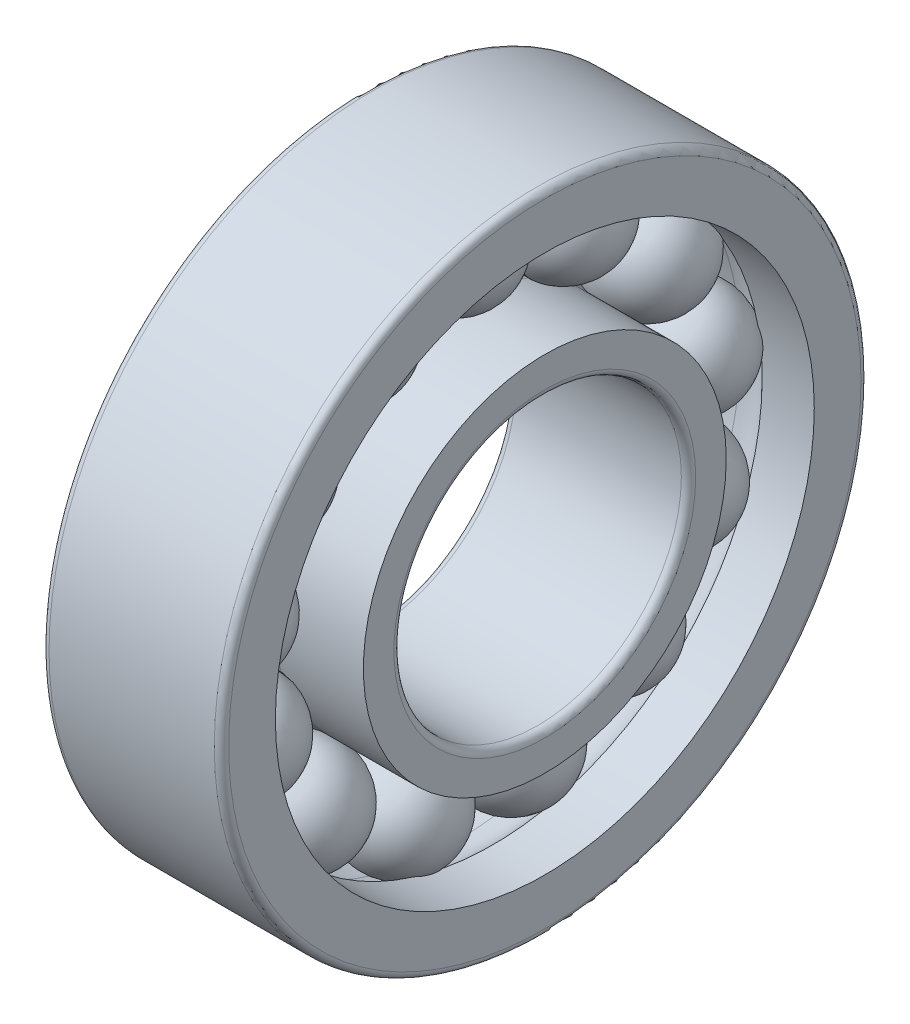
SolidWorks part; units mm, degrees
ref_plane "Plane1" through (0, 0, 0) normal (0, 0, 1) x (1, 0, 0)
ref_plane "Plane2" through (0, 0, 0) normal (0, 1, 0) x (1, 0, 0)
ref_plane "Plane3" through (0, 0, 0) normal (1, 0, 0) x (0, 0, -1)
sketch "Clipboard" plane through (0, 0, 0) normal (0, 0, 1) x (1, 0, 0)
  line L0 (-10, 0) -> (10, 0) construction
  line L1 (0, 0) -> (21.7876, -5.0301)
  line L2 (0, 0) -> (3.2495, -0.0567)
  line L3 (0, 0) -> (22.3573, 0.3902)
  line L4 (0, 0) -> (-22.3573, -0.3902)
  dimension "BallCLRad" = 3.25
sketch "CagSpiSke" plane through (0, 0, 0) normal (0, 0, 1) x (1, 0, 0)
  line L0 (0.1875, 3.125) -> (0.1875, 3.375)
  line L1 (0.1875, 3.375) -> (-0.1875, 3.375)
  line L2 (-0.1875, 3.375) -> (-0.1875, 3.125)
  line L3 (-0.1875, 3.125) -> (0.1875, 3.125)
  line L4 (-20.6375, 0) -> (20.6375, 0) construction
  line L5 (0, 0) -> (0, 23.7692) construction
  dimension "OD" = 6.75
  dimension "ID" = 6.25
revolve "CageSpine" add sketch "CagSpiSke" angle 0.001 about L4
ref_axis "Axis1" through (-50, 0, 0) along (1, 0, 0)
sketch "CagBalSke" plane through (0, 0, 0) normal (0, 0, 1) x (1, 0, 0)
  line L0 (-0.825, 3.25) -> (0.825, 3.25)
  line L1 (-1.905, 3.25) -> (1.905, 3.25) construction
  line L2 (-10, 0) -> (10, 0) construction
  line L3 (0, 0) -> (0, 24) construction
  arc A0 (0.825, 3.25) -> (-0.825, 3.25) centre (0, 3.25) cw
  dimension "BallCLRad" = 3.25
revolve "CageBall" [suppressed] add sketch "CagBalSke" angle 360 about L1 reverse direction yes
pattern_circular "CageBalls" [suppressed] count 13 every 27.692 about axis through (-50, 0, 0) along (1, 0, 0)
sketch "CagTrmODSke" plane through (0, 0, 0) normal (0, 0, 1) x (1, 0, 0)
  line L0 (0.826, 3.375) -> (0.826, 4.076)
  line L1 (0.826, 4.076) -> (-0.826, 4.076)
  line L2 (-0.826, 4.076) -> (-0.826, 3.375)
  line L3 (-0.826, 3.375) -> (0.826, 3.375)
  line L4 (-20.6375, 0) -> (20.6375, 0) construction
  line L5 (0, 0) -> (0, 25) construction
  dimension "Width" = 1.652
  dimension "ID" = 6.75
  dimension "OD" = 8.152
revolve "CageTrimOD" [suppressed] cut sketch "CagTrmODSke" angle 360 about L4 reverse direction yes
sketch "CagTrmIDSke" plane through (0, 0, 0) normal (0, 0, 1) x (1, 0, 0)
  line L0 (0.826, 2.426) -> (0.826, 3.125)
  line L1 (0.826, 3.125) -> (-0.826, 3.125)
  line L2 (-0.826, 3.125) -> (-0.826, 2.426)
  line L3 (-0.826, 2.426) -> (0.826, 2.426)
  line L4 (-20.6375, 0) -> (20.6375, 0) construction
  line L5 (0, 0) -> (0, 25) construction
  dimension "Width" = 1.652
  dimension "ID" = 4.852
  dimension "OD" = 6.25
revolve "CageTrimID" [suppressed] cut sketch "CagTrmIDSke" angle 360 about L4 reverse direction yes
sketch "BalSimSke" plane through (0, 0, 0) normal (0, 0, 1) x (1, 0, 0)
  line L0 (-10, 0) -> (10, 0) construction
  line L1 (-10, 3.25) -> (10, 3.25) construction
  line L2 (0, 0) -> (0, 23) construction
  circle A0 centre (0, 3.25) radius 0.75
  dimension "BallCLRad" = 3.25
  dimension "Ball_diameter" = 1.5
revolve "BallsSimplified" [suppressed] add sketch "BalSimSke" angle 360 about L0
sketch "BalDetSke" plane through (0, 0, 0) normal (0, 0, 1) x (1, 0, 0)
  line L0 (-0.75, 3.25) -> (0.75, 3.25)
  line L1 (-1.905, 3.25) -> (1.905, 3.25) construction
  line L2 (0, 0) -> (0, 25) construction
  arc A0 (0.75, 3.25) -> (-0.75, 3.25) centre (0, 3.25) cw
  dimension "BallCLRad" = 3.25
  dimension "Ball_diameter" = 1.5
revolve "BallDetailed" add sketch "BalDetSke" angle 360 about L1 reverse direction yes
sketch "InnRacSke" plane through (0, 0, 0) normal (0, 0, 1) x (1, 0, 0)
  line L0 (-0.525, 2.75) -> (-1.25, 2.75)
  line L1 (-1.25, 2.75) -> (-1.25, 2.1)
  line L2 (-1.15, 2) -> (1.15, 2)
  line L3 (1.25, 2.1) -> (1.25, 2.525)
  line L4 (0, 2.525) -> (1.25, 2.525)
  line L5 (-20.6375, 0) -> (20.6375, 0) construction
  line L6 (0, 0) -> (0, 30) construction
  arc A0 (-1.25, 2.1) -> (-1.15, 2) centre (-1.15, 2.1) ccw
  arc A1 (1.15, 2) -> (1.25, 2.1) centre (1.15, 2.1) ccw
  arc A2 (0, 2.525) -> (-0.525, 2.75) centre (0, 3.25) cw
  dimension "BallCLRad" = 3.25
  dimension "Fillet_radius" = 0.1
  dimension "Ball_diameter" = 1.45
  dimension "ID" = 4
  dimension "OD" = 5.5
  dimension "Width" = 2.5
revolve "InnerRace" add sketch "InnRacSke" angle 360 about L5 reverse direction yes
sketch "OutRacSke" plane through (0, 0, 0) normal (0, 0, 1) x (1, 0, 0)
  line L0 (0, 3.975) -> (-1.25, 3.975)
  line L1 (-1.25, 3.975) -> (-1.25, 4.4)
  line L2 (-1.15, 4.5) -> (1.15, 4.5)
  line L3 (1.25, 4.4) -> (1.25, 3.75)
  line L4 (1.25, 3.75) -> (0.525, 3.75)
  line L5 (-20.6375, 0) -> (20.6375, 0) construction
  line L6 (0, 0) -> (0, 30) construction
  arc A0 (-1.25, 4.4) -> (-1.15, 4.5) centre (-1.15, 4.4) cw
  arc A1 (1.15, 4.5) -> (1.25, 4.4) centre (1.15, 4.4) cw
  arc A2 (0.525, 3.75) -> (0, 3.975) centre (0, 3.25) ccw
  dimension "BallCLRad" = 3.25
  dimension "Fillet_radius" = 0.1
  dimension "Ball_diameter" = 1.45
  dimension "Width" = 2.5
revolve "OuterRace" add sketch "OutRacSke" angle 360 about L5 reverse direction yes
pattern_circular "BallsDetailed" count 13 every 27.692 about axis through (-50, 0, 0) along (1, 0, 0) of "BallDetailed"
equation "\"BallCLRad@Clipboard\" = ( \"OD@OutRacSke\" + \"ID@InnRacSke\" ) / 4"
equation "\"BallCLRad@BalSimSke\" = \"BallCLRad@Clipboard\""
equation "\"BallCLRad@BalDetSke\" = \"BallCLRad@Clipboard\""
equation "\"BallCLRad@InnRacSke\" = \"BallCLRad@Clipboard\""
equation "\"BallCLRad@OutRacSke\" = \"BallCLRad@Clipboard\""
equation "\"Ball_diameter@InnRacSke\" = \"Ball_diameter@BalDetSke\" - 0.05"
equation "\"Ball_diameter@OutRacSke\" = \"Ball_diameter@BalDetSke\" - 0.05"
equation "\"Ball_diameter@BalSimSke\" = \"Ball_diameter@BalDetSke\""
equation "\"Width@OutRacSke\" = \"Width@InnRacSke\""
equation "\"Fillet_radius@OutRacSke\" = \"Fillet_radius@InnRacSke\""
equation "\"Max_count@Clipboard\" = int( 3.14159265 / atn(( \"Ball_diameter@BalDetSke\" / 2) / sqr( \"BallCLRad@Clipboard\"  *  \"BallCLRad@Clipboard\" - ( \"Ball_diameter@BalDetSke\" / 2) *  ( \"Ball_diameter@BalDetSke\" / 2))))"
equation "\"Max_count@Clipboard\" = ((sgn( \"Max_count@Clipboard\" - \"Count@Clipboard\" )-1)*( \"Max_count@Clipboard\" - \"Count@Clipboard\" ))/-2+ \"Count@Clipboard\""
equation "\"Count@BallsDetailed\" = int( \"Show_count@Clipboard\" ) "
equation "\"Count@BallsDetailed\" = ((sgn( \"Count@BallsDetailed\" - \"Max_count@Clipboard\" )-1)*( \"Count@BallsDetailed\" - \"Max_count@Clipboard\" ))/-2+ \"Max_count@Clipboard\""
equation "\"Count@BallsDetailed\" = ((sgn( \"Count@BallsDetailed\" - \"Min_count@Clipboard\" )+1)*( \"Count@BallsDetailed\" - \"Min_count@Clipboard\"))/2 +\"Min_count@Clipboard\""
equation "\"Angle@BallsDetailed\" = 360.0 / \"Max_count@Clipboard\""
equation "\"BallCLRad@CagBalSke\" = \"BallCLRad@Clipboard\""
equation "\"Count@CageBalls\" = \"Count@BallsDetailed\""
equation "\"Angle@CageBalls\" = \"Angle@BallsDetailed\""
equation "\"Angle@CageSpine\" =  \"Angle@CageBalls\" * ( \"Count@CageBalls\" -1 + int( \"Count@CageBalls\" / \"Max_count@Clipboard\" ) )  + 0.001 -  int( \"Count@CageBalls\" / \"Max_count@Clipboard\" ) * 0.001"
equation "\"Angle@CageSpine\" =  \"Angle@CageSpine\" * int( \"Min_count@Clipboard\" / 2) + int(1 / \"Min_count@Clipboard\")  * 0.001"
equation "\"CageWallOD@CagBalSke\" =  \"Ball_diameter@BalDetSke\" * 1.1"
equation "\"Thickness@CagSpiSke\" =  \"Ball_diameter@BalDetSke\" * 0.25"
equation "\"OD@CagTrmODSke\" = \"BallCLRad@Clipboard\" * 2 + \"CageWallOD@CagBalSke\" + 0.002"
equation "\"ID@CagTrmODSke\" = \"BallCLRad@Clipboard\" * 2 + \"Ball_diameter@BalDetSke\" / 6"
equation "\"OD@CagTrmIDSke\" = \"BallCLRad@Clipboard\" * 2 - \"Ball_diameter@BalDetSke\" / 6"
equation "\"ID@CagTrmIDSke\" = \"BallCLRad@Clipboard\" * 2 - \"CageWallOD@CagBalSke\" + 0.002"
equation "\"OD@CagSpiSke\" = \"ID@CagTrmODSke\""
equation "\"ID@CagSpiSke\" = \"OD@CagTrmIDSke\""
equation "\"Width@CagTrmODSke\" = \"CageWallOD@CagBalSke\" + 0.002"
equation "\"Width@CagTrmIDSke\" = \"CageWallOD@CagBalSke\" + 0.002"
